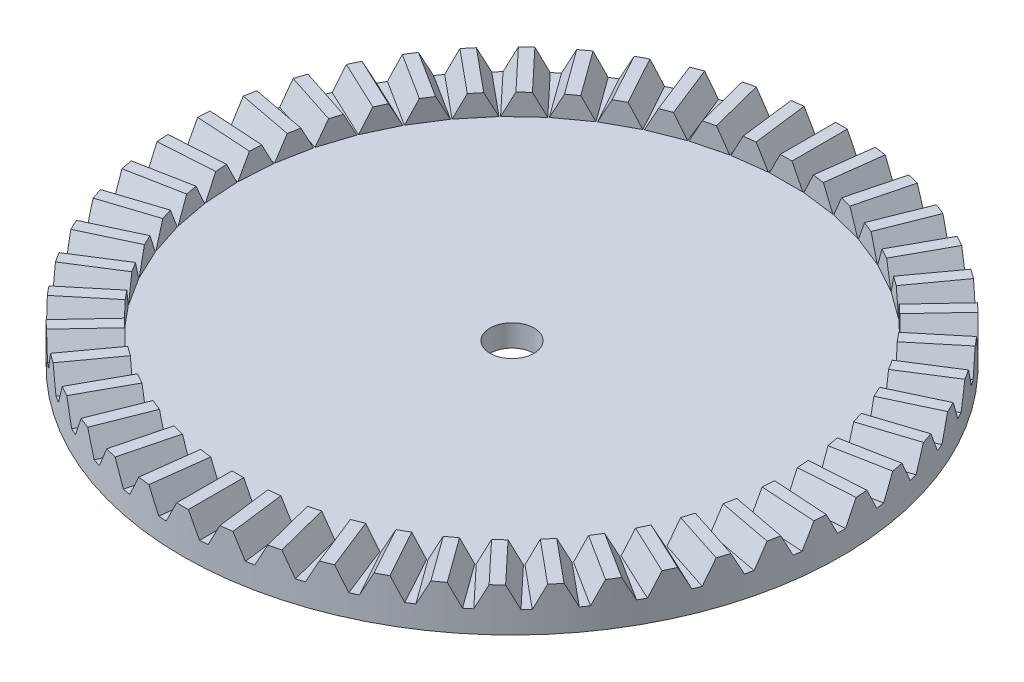
SolidWorks part; units mm, degrees
ref_plane "Front Plane" through (0, 0, 0) normal (0, 0, 1) x (1, 0, 0)
ref_plane "Top Plane" through (0, 0, 0) normal (0, 1, 0) x (1, 0, 0)
ref_plane "Right Plane" through (0, 0, 0) normal (1, 0, 0) x (0, 0, -1)
sketch "Foot Measurements" [suppressed] plane through (0, 0, 0) normal (0, 1, 0) x (1, 0, 0)
  line L0 (0, 0) -> (0, 73) construction
  line L1 (0, 0) -> (0, 147) construction
  line L2 (0, 0) -> (33, 0) construction
  line L3 (0, 0) -> (75, 0) construction
  line L4 (0, 73) -> (33, 73) construction
  line L5 (33, 73) -> (33, 0) construction
  line L6 (0, 147) -> (75, 147) construction
  line L7 (75, 147) -> (75, 0) construction
  line L8 (0, -100) -> (250, -100) construction
  line L9 (0, -100) -> (173, -100) construction
  dimension "D1" = 33
  dimension "D2" = 75
  dimension "D3" = 73
  dimension "D4" = 147
sketch "Sketch3" plane through (0, 0, 0) normal (0, 1, 0) x (1, 0, 0)
  circle A0 centre (0, 0) radius 30
extrude "Boss-Extrude3" add sketch "Sketch3" along normal blind 2
sketch "Sketch6" plane through (0, 2, 0) normal (0, 1, 0) x (1, 0, 0)
  circle A1 centre (0, 0) radius 2
  dimension "D1" = 4
extrude "Cut-Extrude1" cut sketch "Sketch6" against normal up to next
sketch "Sketch5" plane through (0, 2, 0) normal (0, 1, 0) x (1, 0, 0)
  line L3 (-1.5701, 29.9589) -> (-1.5701, 24.9589)
  line L4 (0, 0) -> (-1.5701, 29.9589) construction
  line L5 (0, 0) -> (1.5701, 29.9589) construction
  line L6 (-1.5701, 24.9589) -> (1.5701, 24.9589)
  line L7 (1.5701, 24.9589) -> (1.5701, 29.9589)
  arc A0 (1.5701, 29.9589) -> (-1.5701, 29.9589) centre (0, 0) ccw
  dimension "D2" = 5
  dimension "D1" = 6
  dimension "D3" = 3.1402
extrude "Boss-Extrude5" add sketch "Sketch5" along normal blind 3
sketch "Sketch14" plane through (0, 0, -24.9589) normal (0, 0, 1) x (1, 0, 0)
  line L1 (-1.5701, 2) -> (-1.5701, 5)
  line L2 (-1.5701, 5) -> (1.5701, 5)
  line L3 (1.5701, 2) -> (1.5201, 2)
  line L4 (1.5701, 5) -> (1.5701, 2)
  line L5 (1.5201, 2) -> (0.532, 3.95)
  line L6 (-1.5701, 2) -> (-1.5201, 2)
  line L7 (-1.5201, 2) -> (-0.532, 3.95)
  line L10 (0.532, 3.95) -> (-0.532, 3.95)
extrude "Cut-Extrude4" cut sketch "Sketch14" against normal up to next contours L10 L5 L3 L4 L2 L1 L6 L7 region at (0, 4.0032, -24.9589)
pattern_circular "CirPattern2" count 50 over 360 about axis through (0, -0.001, 0) along (0, 1, 0) of "Cut-Extrude4", "Boss-Extrude5"
